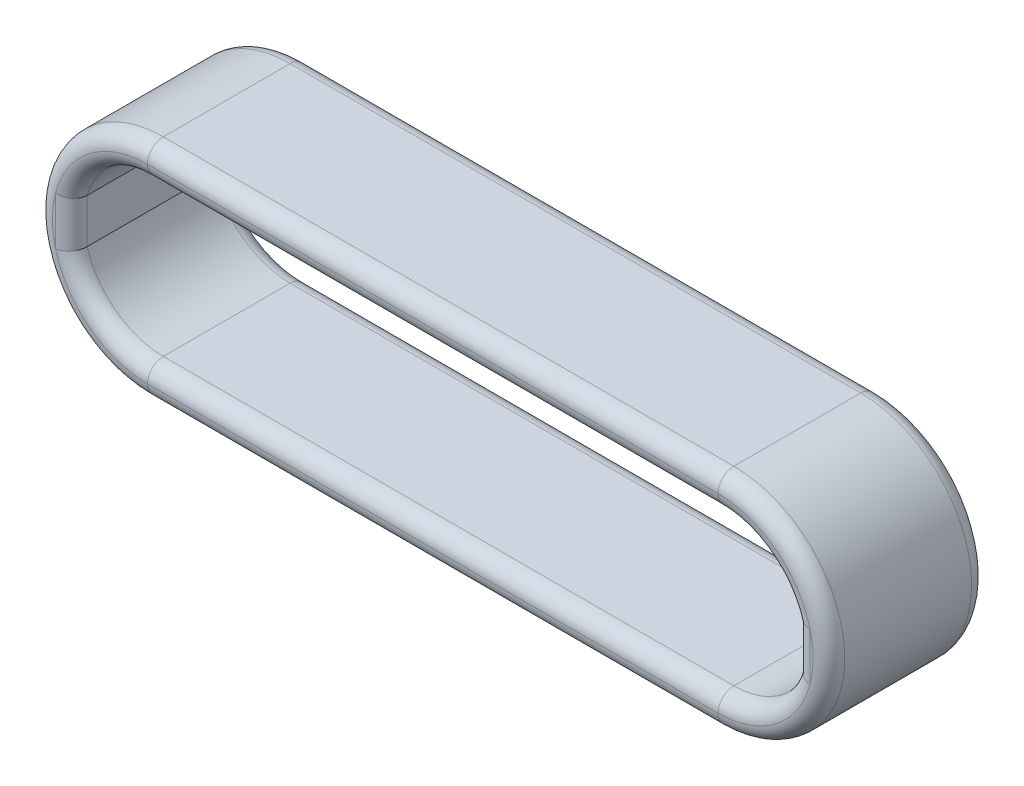
SolidWorks part; units mm, degrees
ref_plane "Front Plane" through (0, 0, 0) normal (0, 0, 1) x (1, 0, 0)
ref_plane "Top Plane" through (0, 0, 0) normal (0, 1, 0) x (1, 0, 0)
ref_plane "Right Plane" through (0, 0, 0) normal (1, 0, 0) x (0, 0, -1)
sketch "Sketch1" plane through (0, 0, 0) normal (0, 0, 1) x (1, 0, 0)
  line L0 (-9, 0) -> (9, 0) construction
  line L1 (-9, 2.5) -> (9, 2.5)
  line L2 (-9, -2.5) -> (9, -2.5)
  line L3 (-9, 0) -> (9, 0) construction
  line L4 (-9, 3.5) -> (9, 3.5)
  line L5 (-9, -3.5) -> (9, -3.5)
  line L6 (-11.4, 0.7) -> (-11.4, -0.7)
  line L7 (0, -55) -> (0, 55) construction
  line L8 (11.4, 0.7) -> (11.4, -0.7)
  arc A0 (-9, 2.5) -> (-11.4, 0.7) centre (-9, 0) ccw
  arc A1 (9, -2.5) -> (11.4, -0.7) centre (9, 0) ccw
  arc A2 (-9, 3.5) -> (-9, -3.5) centre (-9, 0) ccw
  arc A3 (9, -3.5) -> (9, 3.5) centre (9, 0) ccw
  arc A4 (-11.4, -0.7) -> (-9, -2.5) centre (-9, 0) ccw
  arc A5 (11.4, 0.7) -> (9, 2.5) centre (9, 0) ccw
  point P3 (0, 0)
  point P8 (0, 0)
  point P17 (-10.7125, -1.8214)
  dimension "D1" = 18
  dimension "D2" = 5
  dimension "D3" = 1
  dimension "D4" = 2.4
extrude "Boss-Extrude1" add sketch "Sketch1" along normal blind 5
fillet "Fillet1" radius 0.5 24 edges at (0, 2.5, 0) (10.5, -2, 0) (0, -2.5, 0) (-10.5, 2, 0) (0, -3.5, 0) (12.5, 0, 0) (0, 3.5, 0) (-12.5, 0, 0) (10.5, -2, 5) (0, 2.5, 5) (-10.5, 2, 5) (0, -2.5, 5) (0, 3.5, 5) (12.5, 0, 5) (0, -3.5, 5) (-12.5, 0, 5) (10.5, 2, 0) (11.4, 0, 0) (-10.5, -2, 0) (-11.4, 0, 0) (-10.5, -2, 5) (11.4, 0, 5) (10.5, 2, 5) (-11.4, 0, 5)
